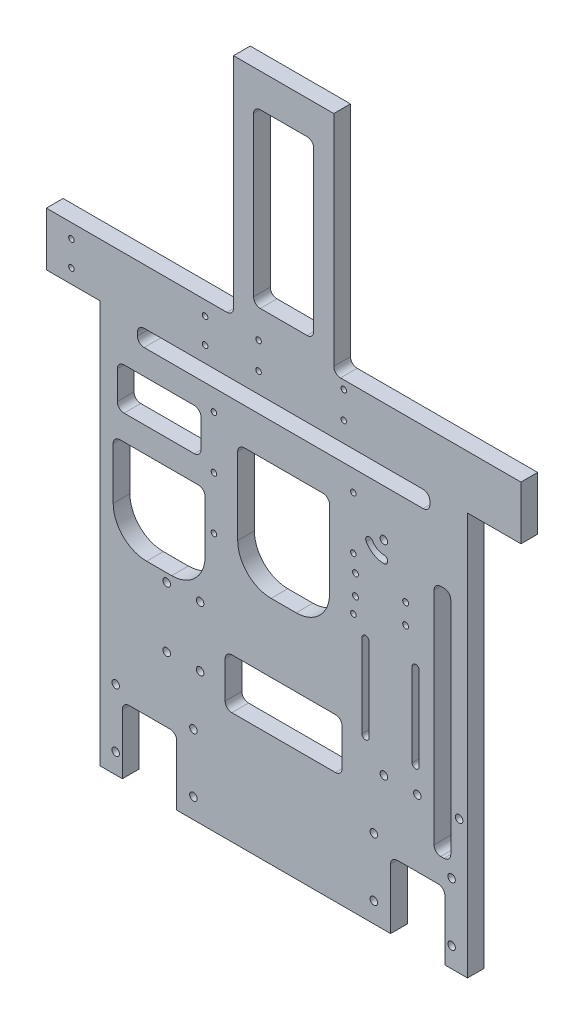
SolidWorks part; units mm, degrees
ref_plane "Front" through (0, 0, 0) normal (0, 0, 1) x (1, 0, 0)
ref_plane "Top" through (0, 0, 0) normal (0, 1, 0) x (1, 0, 0)
ref_plane "Right" through (0, 0, 0) normal (1, 0, 0) x (0, 0, -1)
sketch "Esquisse1" plane through (0, 0, 0) normal (0, 0, 1) x (1, 0, 0)
  line L1 (0, 0) -> (220, 0)
  line L2 (0, 0) -> (0, 285)
  line L3 (0, 285) -> (220, 285)
  line L4 (220, 0) -> (220, 285)
  dimension "D1" = 220
  dimension "D2" = 285
extrude "Boss.-Extru.1" add sketch "Esquisse1" along normal blind 10
sketch "Esquisse2" plane through (0, 0, 0) normal (0, -1, 0) x (1, 0, 0)
  line L0 (0, 5) -> (220, 5) construction
  line L1 (0, 10) -> (0, 0) construction
  line L2 (220, 10) -> (220, 0) construction
  line L3 (110, 5) -> (110, 28.0559) construction
  circle A0 centre (110, 5) radius 2
  circle A1 centre (213, 5) radius 2
  circle A2 centre (7, 5) radius 2
  dimension "D1" = 4
  dimension "D2" = 103
extrude "Enlèv. mat.-Extru.1" cut sketch "Esquisse2" against normal blind 8
sketch "Esquisse3" plane through (0, 0, 10) normal (0, 0, 1) x (1, 0, 0)
  line L0 (110, 0) -> (110, 285) construction
  line L1 (0, 0) -> (220, 0) construction
  line L2 (220, 285) -> (0, 285) construction
  line L3 (82.5, 208) -> (137.5, 208)
  line L4 (137.5, 208) -> (137.5, 138)
  line L5 (137.5, 138) -> (82.5, 138)
  line L6 (82.5, 208) -> (82.5, 138)
  line L8 (8, 175) -> (63, 175)
  line L9 (8, 175) -> (8, 120)
  line L10 (8, 120) -> (63, 120)
  line L11 (63, 175) -> (63, 120)
  line L12 (200, 55) -> (210, 55)
  line L13 (200, 55) -> (200, 195)
  line L14 (200, 195) -> (210, 195)
  line L15 (210, 55) -> (210, 195)
  point P11 (110, 138)
  point P12 (110, 208)
  dimension "D1" = 70
  dimension "D2" = 55
  dimension "D3" = 138
  dimension "D4" = 55
  dimension "D5" = 47
  dimension "D6" = 55
  dimension "D7" = 120
  dimension "D8" = 140
  dimension "D9" = 55
  dimension "D10" = 90
  dimension "D11" = 10
extrude "Enlèv. mat.-Extru.2" cut sketch "Esquisse3" against normal through all both and the other way through all
sketch "Esquisse5" plane through (0, 0, 10) normal (0, 0, 1) x (1, 0, 0)
  line L0 (110, 230) -> (110, 0) construction
  line L1 (22.5, 240) -> (197.5, 240)
  line L2 (22.5, 240) -> (22.5, 230)
  line L3 (22.5, 230) -> (197.5, 230)
  line L4 (197.5, 240) -> (197.5, 230)
  line L5 (0, 0) -> (220, 0) construction
  dimension "D1" = 175
  dimension "D2" = 10
  dimension "D3" = 230
extrude "Enlèv. mat.-Extru.3" cut sketch "Esquisse5" against normal through all both and the other way through all
sketch "Esquisse6" plane through (0, 0, 10) normal (0, 0, 1) x (1, 0, 0)
  line L0 (170, 80) -> (190, 80) construction
  line L1 (0, 0) -> (220, 0) construction
  line L2 (137.5, 138) -> (82.5, 138) construction
  line L3 (215, 80) -> (190, 80) construction
  line L4 (168, 193.9299) -> (168, 170.25) construction
  line L5 (186.4274, 170.25) -> (149.5726, 170.25) construction
  line L6 (0, 285) -> (0, 0) construction
  circle A0 centre (190, 80) radius 2.25
  circle A1 centre (170, 80) radius 2.25
  circle A2 centre (215, 80) radius 2.25
  circle A3 centre (153, 176.25) radius 1.75
  circle A4 centre (183, 176.25) radius 1.75
  circle A5 centre (183, 164.25) radius 1.75
  circle A6 centre (153, 164.25) radius 1.75
  point P8 (110, 138)
  dimension "D1" = 4.5
  dimension "D3" = 80
  dimension "D6" = 30
  dimension "D7" = 12
  dimension "D8" = 3.5
  dimension "D2" = 20
  dimension "D4" = 60
  dimension "D5" = 25
  dimension "D9" = 168
  dimension "D10" = 170.25
extrude "Enlèv. mat.-Extru.4" cut sketch "Esquisse6" against normal through all both and the other way through all
sketch "Esquisse7" plane through (0, 0, 10) normal (0, 0, 1) x (1, 0, 0)
  line L0 (110, 0) -> (110, 285) construction
  line L1 (0, 0) -> (220, 0) construction
  line L2 (220, 285) -> (0, 285) construction
  line L3 (68.285, 186) -> (68.285, 217.4) construction
  line L4 (68.285, 186) -> (110, 186) construction
  line L5 (151.715, 186) -> (151.715, 217.4) construction
  line L6 (95, 268) -> (120.5, 268) construction
  line L7 (120.5, 268) -> (120.5, 260) construction
  line L8 (120.5, 260) -> (137.9818, 260) construction
  line L9 (95, 252) -> (120.5, 252) construction
  line L10 (22.5, 240) -> (197.5, 240) construction
  circle A0 centre (68.285, 217.4) radius 1.65
  circle A1 centre (68.285, 186) radius 1.65
  circle A2 centre (68.285, 154.6) radius 1.65
  circle A3 centre (151.715, 154.6) radius 1.65
  circle A4 centre (151.715, 186) radius 1.65
  circle A5 centre (151.715, 217.4) radius 1.65
  circle A6 centre (95, 268) radius 1.65
  circle A7 centre (146, 268) radius 1.65
  circle A8 centre (146, 252) radius 1.65
  circle A9 centre (95, 252) radius 1.65
  dimension "D1" = 31.4
  dimension "D2" = 3.3
  dimension "D5" = 16
  dimension "D6" = 51
  dimension "D9" = 3.3
  dimension "D7" = 15
  dimension "D3" = 83.43
  dimension "D4" = 186
  dimension "D8" = 20
extrude "Enlèv. mat.-Extru.5" cut sketch "Esquisse7" against normal through all both and the other way through all
sketch "Esquisse8" plane through (0, 0, 10) normal (0, 0, 1) x (1, 0, 0)
  line L0 (110, 0) -> (110, 285) construction
  line L1 (0, 0) -> (220, 0) construction
  line L2 (220, 285) -> (0, 285) construction
  line L3 (174, 0) -> (174, 40)
  line L4 (13.5, 0) -> (46, 0)
  line L5 (13.5, 0) -> (13.5, 40)
  line L6 (13.5, 40) -> (46, 40)
  line L7 (46, 0) -> (46, 40)
  line L8 (206.5, 40) -> (174, 40)
  line L9 (206.5, 0) -> (206.5, 40)
  line L10 (206.5, 0) -> (174, 0)
  dimension "D1" = 128
  dimension "D2" = 32.5
  dimension "D3" = 40
extrude "Enlèv. mat.-Extru.6" cut sketch "Esquisse8" against normal through all both and the other way through all
fillet "Congé1" radius 20 4 edges at (137.5, 138, 5) (82.5, 138, 5) (63, 120, 5) (8, 120, 5)
sketch "Esquisse9" plane through (0, 0, 10) normal (0, 0, 1) x (1, 0, 0)
  line L0 (189, 145) -> (189, 95) construction
  line L1 (191.1, 145) -> (191.1, 95)
  line L2 (186.9, 145) -> (186.9, 95)
  line L3 (189, 120) -> (159, 120) construction
  line L4 (174, 120) -> (174, 121.5076) construction
  line L5 (159, 95) -> (159, 145) construction
  line L6 (156.9, 95) -> (156.9, 145)
  line L7 (161.1, 95) -> (161.1, 145)
  line L9 (210, 55) -> (200, 55) construction
  line L10 (200, 55) -> (200, 195) construction
  arc A0 (191.1, 145) -> (186.9, 145) centre (189, 145) ccw
  arc A1 (186.9, 95) -> (191.1, 95) centre (189, 95) ccw
  arc A2 (156.9, 95) -> (161.1, 95) centre (159, 95) ccw
  arc A3 (161.1, 145) -> (156.9, 145) centre (159, 145) ccw
  point P2 (189, 120)
  point P13 (159, 120)
  dimension "D1" = 4.2
  dimension "D2" = 30
  dimension "D3" = 11
  dimension "D4" = 40
  dimension "D5" = 50
extrude "Enlèv. mat.-Extru.7" cut sketch "Esquisse9" against normal through all both and the other way through all
sketch "Esquisse10" plane through (0, 0, 10) normal (0, 0, 1) x (1, 0, 0)
  line L0 (9.5, 0) -> (9.5, 52.9697) construction
  line L1 (0, 0) -> (13.5, 0) construction
  line L2 (0, 285) -> (0, 0) construction
  line L3 (110, 0) -> (110, 48.9194) construction
  line L4 (46, 0) -> (174, 0) construction
  line L5 (32.75, 0) -> (32.75, 52.9697) construction
  circle A0 centre (9.5, 12) radius 2.25
  circle A1 centre (9.5, 47) radius 2.25
  circle A2 centre (210.5, 47) radius 2.25
  circle A3 centre (210.5, 12) radius 2.25
  circle A4 centre (56, 47) radius 2.25
  circle A5 centre (56, 12) radius 2.25
  circle A6 centre (164, 12) radius 2.25
  circle A7 centre (164, 47) radius 2.25
  dimension "D2" = 4.5
  dimension "D3" = 35
  dimension "D4" = 12
  dimension "D5" = 46.5
  dimension "D1" = 9.5
extrude "Enlèv. mat.-Extru.8" cut sketch "Esquisse10" against normal through all both and the other way through all
sketch "Esquisse11" plane through (0, 0, 10) normal (0, 0, 1) x (1, 0, 0)
  line L0 (110, 67) -> (110, 0) construction
  line L1 (75, 97) -> (145, 97)
  line L2 (75, 97) -> (75, 67)
  line L3 (75, 67) -> (145, 67)
  line L4 (145, 97) -> (145, 67)
  line L5 (46, 0) -> (174, 0) construction
  dimension "D1" = 70
  dimension "D2" = 30
  dimension "D3" = 67
extrude "Enlèv. mat.-Extru.9" cut sketch "Esquisse11" against normal through all both and the other way through all
sketch "Esquisse12" plane through (0, 0, 10) normal (0, 0, 1) x (1, 0, 0)
  line L0 (220, 0) -> (220, 285) construction
  line L1 (46, 0) -> (174, 0) construction
  line L2 (170, 202) -> (161.3397, 197) construction
  line L3 (170, 192) -> (170, 202) construction
  circle A0 centre (170, 202) radius 2.25
  arc A1 (161.3397, 197) -> (170, 192) centre (170, 202) ccw construction
  arc A2 (159.3912, 195.875) -> (170, 189.75) centre (170, 202) ccw
  arc A3 (163.2883, 198.125) -> (170, 194.25) centre (170, 202) ccw
  arc A4 (163.2883, 198.125) -> (159.3912, 195.875) centre (161.3397, 197) ccw
  arc A5 (170, 189.75) -> (170, 194.25) centre (170, 192) ccw
  point P9 (165, 193.3397)
  dimension "D1" = 4.5
  dimension "D2" = 50
  dimension "D3" = 202
  dimension "D4" = 4.5
  dimension "D5" = 10
  dimension "D6" = 60
extrude "Enlèv. mat.-Extru.10" cut sketch "Esquisse12" against normal through all both and the other way through all
sketch "Esquisse13" plane through (0, 0, 10) normal (0, 0, 1) x (1, 0, 0)
  line L0 (50, 123.132) -> (50, 97) construction
  line L1 (50, 97) -> (30.3926, 97) construction
  line L2 (46, 0) -> (174, 0) construction
  line L3 (0, 285) -> (0, 0) construction
  circle A0 centre (40, 115) radius 2.25
  circle A1 centre (60, 115) radius 2.25
  circle A2 centre (60, 79) radius 2.25
  circle A3 centre (40, 79) radius 2.25
  dimension "D1" = 36
  dimension "D2" = 20
  dimension "D3" = 4.5
  dimension "D4" = 97
  dimension "D5" = 40
extrude "Enlèv. mat.-Extru.11" cut sketch "Esquisse13" against normal through all both and the other way through all
sketch "Esquisse14" plane through (0, 0, 10) normal (0, 0, 1) x (1, 0, 0)
  line L0 (110, 0) -> (110, 159.9943) construction
  line L1 (0, 285) -> (80, 285)
  line L2 (0, 285) -> (0, 273)
  line L3 (0, 273) -> (80, 273)
  line L4 (80, 285) -> (80, 273)
  line L5 (46, 0) -> (174, 0) construction
  line L6 (140, 285) -> (140, 273)
  line L7 (220, 273) -> (140, 273)
  line L8 (220, 285) -> (220, 273)
  line L9 (220, 285) -> (140, 285)
  dimension "D1" = 12
  dimension "D2" = 80
extrude "Enlèv. mat.-Extru.12" cut sketch "Esquisse14" against normal through all both and the other way through all
sketch "Esquisse15" plane through (0, 0, 10) normal (0, 0, 1) x (1, 0, 0)
  line L0 (140, 285) -> (80, 285) construction
  line L1 (80, 285) -> (140, 285)
  line L2 (80, 285) -> (80, 408)
  line L3 (80, 408) -> (140, 408)
  line L4 (140, 285) -> (140, 408)
  line L5 (110, 408) -> (110, 0) construction
  line L6 (46, 0) -> (174, 0) construction
  dimension "D1" = 60
  dimension "D2" = 123
extrude "Boss.-Extru.2" add sketch "Esquisse15" against normal up to vertex (10 mm away) up to point (13.5, 0, 0)
sketch "Esquisse16" plane through (0, 0, 10) normal (0, 0, 1) x (1, 0, 0)
  line L0 (110, 388) -> (110, 408) construction
  line L1 (92, 285) -> (128, 285)
  line L2 (92, 285) -> (92, 388)
  line L3 (92, 388) -> (128, 388)
  line L4 (128, 285) -> (128, 388)
  line L5 (140, 408) -> (80, 408) construction
  line L6 (140, 273) -> (140, 408) construction
  line L7 (80, 273) -> (0, 273) construction
  dimension "D1" = 12
  dimension "D2" = 20
  dimension "D3" = 12
extrude "Enlèv. mat.-Extru.13" cut sketch "Esquisse16" against normal through all both and the other way through all
sketch "Esquisse17" plane through (0, 0, 10) normal (0, 0, 1) x (1, 0, 0)
  line L0 (110, 0) -> (110, -39.2027) construction
  line L1 (220, 273) -> (252, 273)
  line L2 (220, 273) -> (220, 241)
  line L3 (220, 241) -> (252, 241)
  line L4 (252, 273) -> (252, 241)
  line L5 (46, 0) -> (174, 0) construction
  line L6 (-32, 273) -> (-32, 241)
  line L7 (0, 241) -> (-32, 241)
  line L8 (0, 273) -> (0, 241)
  line L9 (0, 273) -> (-32, 273)
  dimension "D1" = 32
  dimension "D2" = 32
extrude "Boss.-Extru.3" add sketch "Esquisse17" against normal up to vertex (10 mm away) up to point (140, 273, 0)
sketch "Esquisse18" plane through (0, 0, 10) normal (0, 0, 1) x (1, 0, 0)
  line L0 (35.5, 190) -> (35.5, 175) construction
  line L1 (10.5, 190) -> (60.5, 190)
  line L2 (10.5, 190) -> (10.5, 215)
  line L3 (10.5, 215) -> (60.5, 215)
  line L4 (60.5, 190) -> (60.5, 215)
  line L5 (8, 175) -> (63, 175) construction
  dimension "D1" = 25
  dimension "D2" = 50
  dimension "D3" = 15
extrude "Enlèv. mat.-Extru.14" cut sketch "Esquisse18" against normal through all both and the other way through all
fillet "Congé2" radius 4 30 edges at (137.5, 208, 5) (82.5, 208, 5) (197.5, 230, 5) (197.5, 240, 5) (22.5, 240, 5) (22.5, 230, 5) (63, 175, 5) (8, 175, 5) (200, 195, 5) (210, 195, 5) (210, 55, 5) (200, 55, 5) (206.5, 40, 5) (174, 40, 5) (46, 40, 5) (13.5, 40, 5) (75, 67, 5) (145, 67, 5) (145, 97, 5) (75, 97, 5) (92, 388, 5) (128, 388, 5) (128, 285, 5) (92, 285, 5) (140, 273, 5) (80, 273, 5) (10.5, 215, 5) (60.5, 215, 5) (60.5, 190, 5) (10.5, 190, 5)
sketch "Esquisse19" plane through (0, 0, 10) normal (0, 0, 1) x (1, 0, 0)
  line L0 (-32, 257) -> (54.3473, 257) construction
  line L1 (-32, 273) -> (-32, 241) construction
  line L2 (23, 257) -> (23, 269.1) construction
  circle A0 centre (-17, 264.5) radius 1.65
  circle A1 centre (-17, 249.5) radius 1.65
  circle A2 centre (63, 249.5) radius 1.65
  circle A3 centre (63, 264.5) radius 1.65
  dimension "D2" = 80
  dimension "D3" = 3.3
  dimension "D1" = 15
  dimension "D4" = 55
extrude "Enlèv. mat.-Extru.15" cut sketch "Esquisse19" against normal through all both and the other way through all
